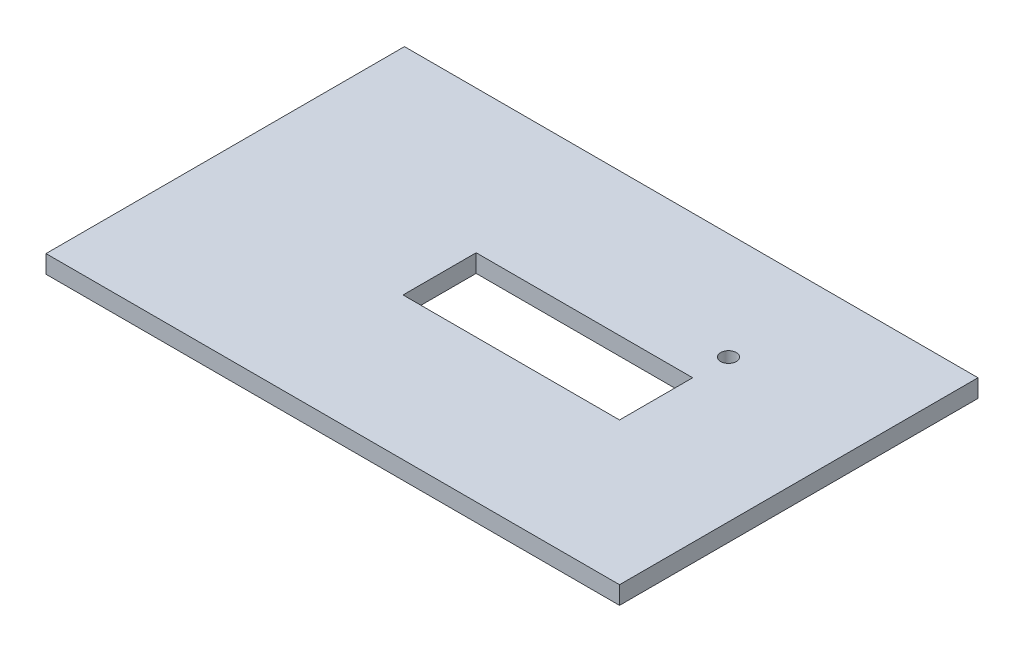
SolidWorks part; units mm, degrees
ref_plane "Front Plane" through (0, 0, 0) normal (0, 0, 1) x (1, 0, 0)
ref_plane "Top Plane" through (0, 0, 0) normal (0, 1, 0) x (1, 0, 0)
ref_plane "Right Plane" through (0, 0, 0) normal (1, 0, 0) x (0, 0, -1)
sketch "Sketch1" plane through (0, 0, 0) normal (0, 1, 0) x (1, 0, 0)
  line L0 (0, 63.5) -> (203.2, 63.5) construction
  line L1 (0, 0) -> (203.2, 0)
  line L2 (0, 0) -> (0, 127)
  line L3 (0, 127) -> (203.2, 127)
  line L4 (203.2, 0) -> (203.2, 127)
  line L5 (152.4, 76.2) -> (76.2, 76.2) construction
  line L6 (152.4, 76.2) -> (152.4, 50.8) construction
  line L7 (152.4, 50.8) -> (76.2, 50.8) construction
  line L8 (76.2, 76.2) -> (76.2, 50.8) construction
  line L9 (152.654, 76.454) -> (75.946, 76.454)
  line L10 (75.946, 76.454) -> (75.946, 50.546)
  line L11 (152.654, 50.546) -> (75.946, 50.546)
  line L12 (152.654, 76.454) -> (152.654, 50.546)
  circle A0 centre (152.654, 89.154) radius 2.7781
  point P11 (154.5204, 86.7643)
  dimension "D7" = 5.5562
  dimension "D1" = 203.2
  dimension "D2" = 127
  dimension "D3" = 127
  dimension "D4" = 25.4
  dimension "D5" = 76.2
  dimension "D8" = 12.7
  dimension "D6" = 0.254
extrude "Boss-Extrude1" add sketch "Sketch1" along normal blind 6.35
